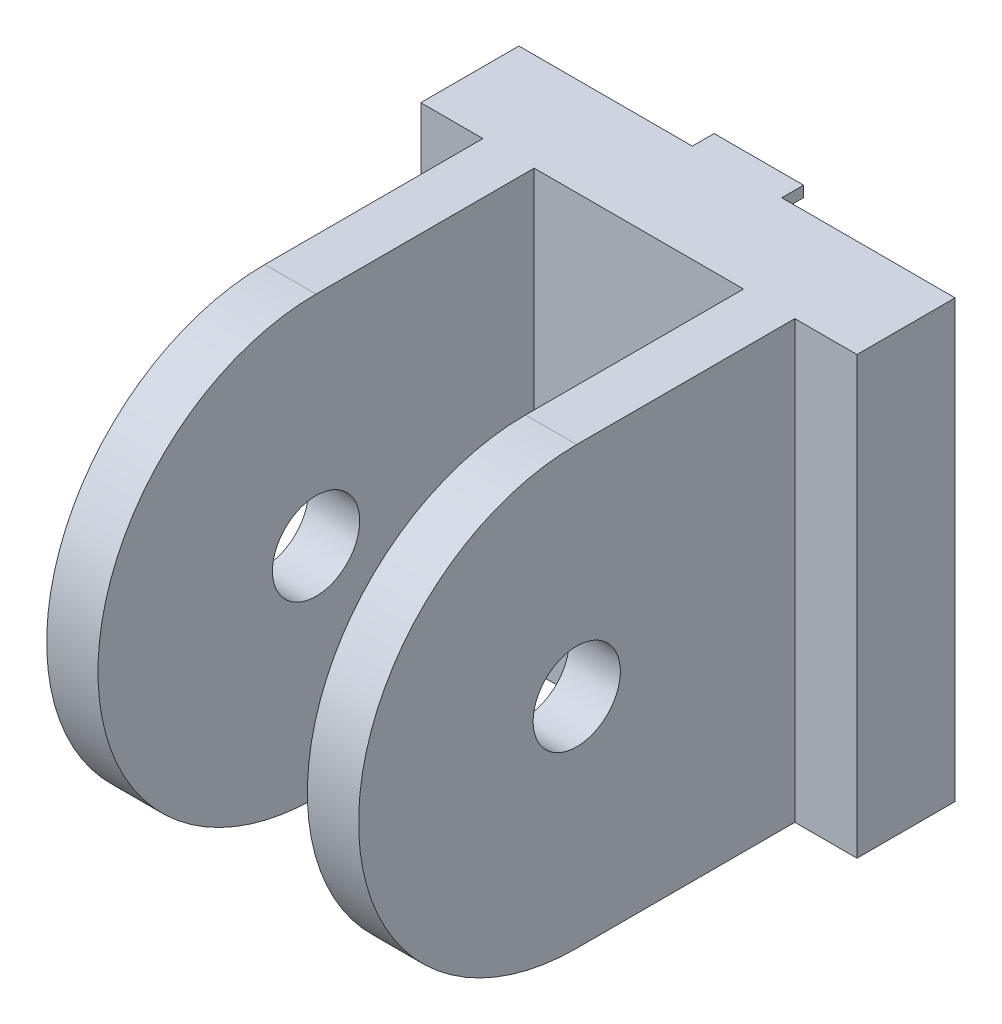
SolidWorks part; units mm, degrees
ref_plane "前视基准面" through (0, 0, 0) normal (0, 0, 1) x (1, 0, 0)
ref_plane "上视基准面" through (0, 0, 0) normal (0, 1, 0) x (1, 0, 0)
ref_plane "右视基准面" through (0, 0, 0) normal (1, 0, 0) x (0, 0, -1)
sketch "草图1" plane through (0, 0, 0) normal (0, 0, 1) x (1, 0, 0)
  line L1 (-20, -20) -> (20, -20)
  line L2 (-20, -20) -> (-20, 20)
  line L3 (-20, 20) -> (20, 20)
  line L4 (20, -20) -> (20, 20)
  line L5 (-20, -20) -> (20, 20) construction
  line L6 (-20, 20) -> (20, -20) construction
  point P0 (0, 0)
  dimension "D1" = 40
  dimension "D2" = 40
extrude "凸台-拉伸1" add sketch "草图1" along normal blind 9
sketch "草图2" plane through (0, 0, 9) normal (0, 0, 1) x (1, 0, 0)
  line L0 (20, 20) -> (-20, 20) construction
  line L1 (-14.3, -20) -> (-9.6, -20)
  line L2 (-14.3, -20) -> (-14.3, 20)
  line L3 (-14.3, 20) -> (-9.6, 20)
  line L4 (-9.6, -20) -> (-9.6, 20)
  line L5 (-14.3, -20) -> (-9.6, 20) construction
  line L6 (-14.3, 20) -> (-9.6, -20) construction
  line L7 (-20, 20) -> (-20, -20) construction
  line L8 (0, 0) -> (0, 12.1648) construction
  line L9 (14.3, -20) -> (9.6, -20)
  line L10 (14.3, -20) -> (14.3, 20)
  line L11 (9.6, -20) -> (9.6, 20)
  line L12 (14.3, 20) -> (9.6, 20)
  point P0 (-11.95, 0)
  dimension "D1" = 4.7
  dimension "D2" = 5.7
extrude "凸台-拉伸2" add sketch "草图2" along normal blind 40
sketch "草图3" plane through (-14.3, 0, 0) normal (-1, 0, 0) x (0, 0, 1)
  line L0 (49, 20) -> (49, -20) construction
  line L1 (49, 20) -> (9, 20) construction
  arc A0 (29, -20) -> (29, 20) centre (29, 0) ccw
  dimension "D1" = 40
extrude "切除-拉伸2" cut sketch "草图3" against normal through all and the other way through all flip side to cut
sketch "草图4" plane through (-14.3, 0, 0) normal (-1, 0, 0) x (0, 0, 1)
  circle A0 centre (29, 0) radius 4
  dimension "D1" = 8
extrude "切除-拉伸3" cut sketch "草图4" against normal through all
sketch "草图6" plane through (0, 0, 9) normal (0, 0, 1) x (1, 0, 0)
  circle A0 centre (0, 0) radius 4
  dimension "D1" = 8
extrude "切除-拉伸5" cut sketch "草图6" against normal through all
sketch "草图7" plane through (0, 0, 0) normal (0, 0, -1) x (-1, 0, 0)
  line L0 (0, 0) -> (-17.0155, 0) construction
  line L1 (-20, 20) -> (20, 20) construction
  line L2 (-4.1, 20) -> (4.1, 20)
  line L3 (-4.1, 20) -> (-4.1, 19)
  line L4 (-4.1, 19) -> (4.1, 19)
  line L5 (4.1, 20) -> (4.1, 19)
  line L6 (4.1, -20) -> (4.1, -19)
  line L7 (-4.1, -20) -> (-4.1, -19)
  line L8 (-4.1, -19) -> (4.1, -19)
  line L9 (-4.1, -20) -> (4.1, -20)
  point P9 (0, 20)
  point P10 (0, 20)
  dimension "D1" = 1
  dimension "D2" = 8.2
extrude "凸台-拉伸3" add sketch "草图7" along normal blind 2
